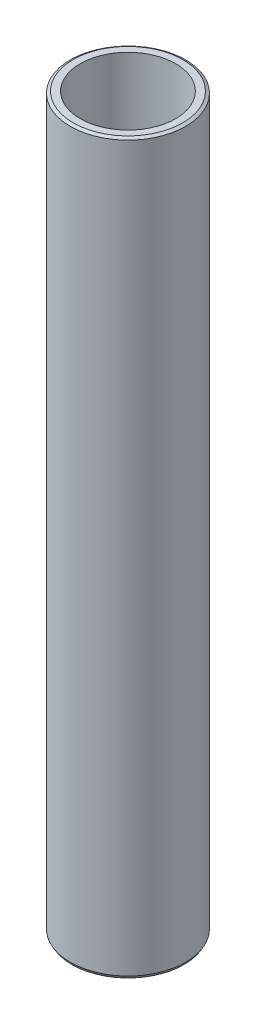
SolidWorks part; units mm, degrees
ref_plane "Front Plane" through (0, 0, 0) normal (0, 0, 1) x (1, 0, 0)
ref_plane "Top Plane" through (0, 0, 0) normal (0, 1, 0) x (1, 0, 0)
ref_plane "Right Plane" through (0, 0, 0) normal (1, 0, 0) x (0, 0, -1)
sketch "Sketch1" plane through (0, 0, 0) normal (0, 1, 0) x (1, 0, 0)
  circle A0 centre (0, 0) radius 47.5
  dimension "SHAFT_OD" = 95
extrude "Boss-Extrude1" add sketch "Sketch1" along normal blind 600
sketch "Sketch2" plane through (0, 0, 0) normal (0, 1, 0) x (1, 0, 0)
  circle A0 centre (0, 0) radius 39.2833
  dimension "BORE_D" = 78.5666
extrude "Cut-Extrude1" cut sketch "Sketch2" along normal through all
chamfer "Chamfer1" distance 1.3545 angle 60 2 edges at (0, 600, 47.5) (0, 0, 47.5) first distance on face at (0, 600, 47.5) first distance on face at (0, 0, 39.2833)
